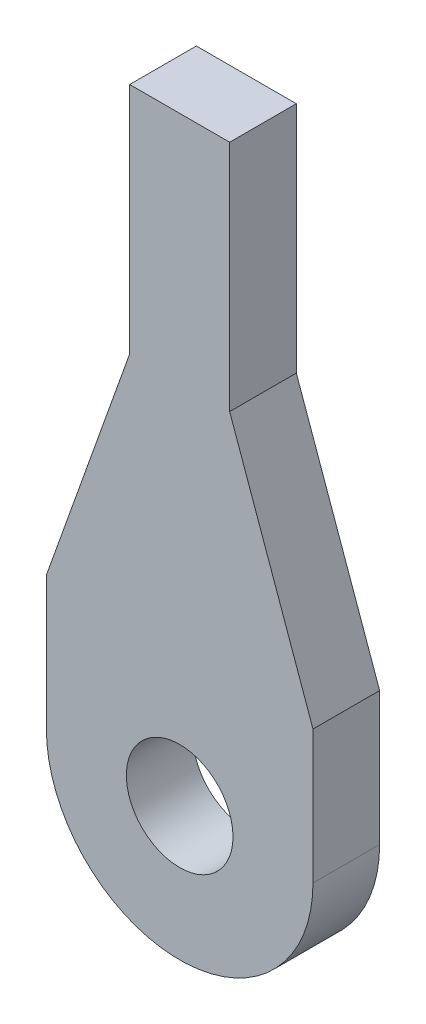
SolidWorks part; units mm, degrees
ref_plane "Front Plane" through (0, 0, 0) normal (1, 0, 0) x (0, 1, 0)
ref_plane "Top Plane" through (0, 0, 0) normal (0, 0, 1) x (0, 1, 0)
ref_plane "Right Plane" through (0, 0, 0) normal (0, 1, 0) x (-1, 0, 0)
sketch "Sketch2" plane through (0, 0, 0) normal (0, 0, 1) x (0, 1, 0)
  line L0 (0, 0) -> (0, 5.08) construction
  line L1 (0, 0) -> (0, -5.08) construction
  line L2 (0, 5.08) -> (5.08, 5.08)
  line L3 (5.08, 5.08) -> (5.08, -5.08) construction
  line L4 (5.08, -5.08) -> (0, -5.08)
  line L5 (5.08, 5.08) -> (13.97, 1.905)
  line L6 (13.97, 1.905) -> (13.97, -1.905) construction
  line L7 (13.97, -1.905) -> (5.08, -5.08)
  line L8 (5.08, 0) -> (13.97, 0) construction
  line L9 (13.97, 1.905) -> (22.86, 1.905)
  line L10 (22.86, 1.905) -> (22.86, -1.905)
  line L11 (22.86, -1.905) -> (13.97, -1.905)
  arc A0 (0, 5.08) -> (0, -5.08) centre (0, 0) ccw
  circle A1 centre (0, 0) radius 2.032
  dimension "D3" = 4.064
  dimension "D1" = 10.16
  dimension "D2" = 5.08
  dimension "D4" = 3.81
  dimension "D5" = 8.89
  dimension "D6" = 8.89
extrude "Boss-Extrude1" add sketch "Sketch2" along normal blind 2.54
